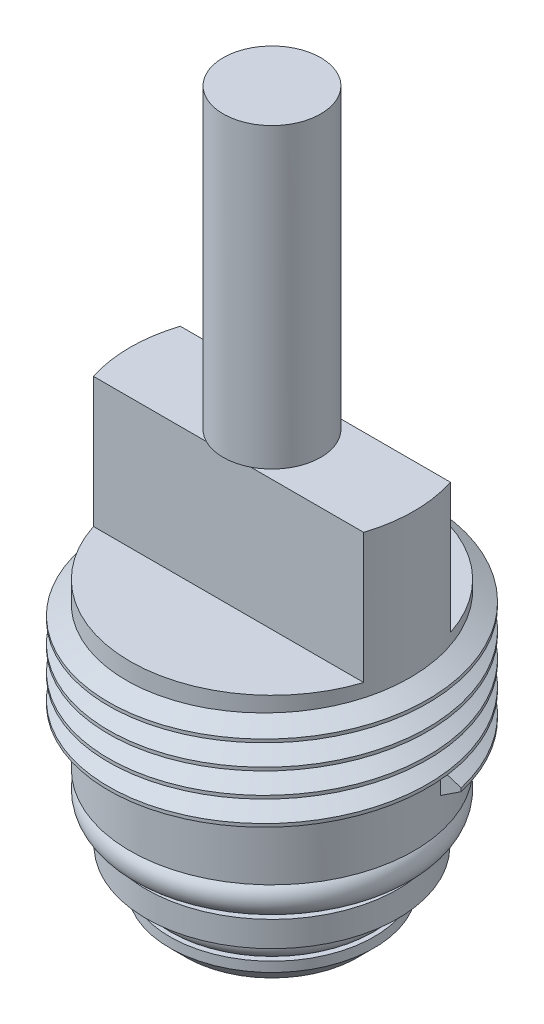
SolidWorks part; units mm, degrees
material "Brass"
ref_plane "Front Plane" through (0, 0, 0) normal (0, 0, 1) x (1, 0, 0)
ref_plane "Top Plane" through (0, 0, 0) normal (0, 1, 0) x (1, 0, 0)
ref_plane "Right Plane" through (0, 0, 0) normal (1, 0, 0) x (0, 0, -1)
sketch "Sketch1" plane through (0, 0, 0) normal (0, 0, 1) x (1, 0, 0)
  line L0 (0, -6751.5455) -> (0, 330825.7272) construction
  line L1 (2.825, -7) -> (-2.825, -7) construction
  line L2 (1.5, 13.675) -> (-1.5, 13.675)
  line L3 (1.5, 13.675) -> (1.5, 4.525)
  line L4 (1.5, 4.525) -> (-1.5, 4.525)
  line L5 (-1.5, 13.675) -> (-1.5, 4.525)
  line L6 (1.5, 13.675) -> (-1.5, 4.525) construction
  line L7 (1.5, 4.525) -> (-1.5, 13.675) construction
  line L8 (3.14, -7.425) -> (-3.14, -7.425)
  line L9 (3.14, -7.425) -> (3.14, -8.225)
  line L10 (3.14, -8.225) -> (-3.14, -8.225)
  line L11 (-3.14, -7.425) -> (-3.14, -8.225)
  line L12 (3.14, -7.425) -> (-3.14, -8.225) construction
  line L13 (3.14, -8.225) -> (-3.14, -7.425) construction
  line L14 (3.87, -5.795) -> (-3.87, -5.795)
  line L15 (3.87, -5.795) -> (3.87, -6.575)
  line L16 (3.87, -6.575) -> (-3.87, -6.575)
  line L17 (-3.87, -5.795) -> (-3.87, -6.575)
  line L18 (3.87, -5.795) -> (-3.87, -6.575) construction
  line L19 (3.87, -6.575) -> (-3.87, -5.795) construction
  line L20 (3.32, -4.525) -> (-3.32, -4.525)
  line L21 (3.32, -4.525) -> (3.32, -5.795)
  line L22 (3.32, -5.795) -> (-3.32, -5.795)
  line L23 (-3.32, -4.525) -> (-3.32, -5.795)
  line L24 (3.32, -4.525) -> (-3.32, -5.795) construction
  line L25 (3.32, -5.795) -> (-3.32, -4.525) construction
  line L26 (4.365, 4.525) -> (-4.365, 4.525)
  line L27 (4.365, 4.525) -> (4.365, -4.525)
  line L28 (4.365, -4.525) -> (-4.365, -4.525)
  line L29 (-4.365, 4.525) -> (-4.365, -4.525)
  line L30 (4.365, 4.525) -> (-4.365, -4.525) construction
  line L31 (4.365, -4.525) -> (-4.365, 4.525) construction
  line L32 (0, 13.675) -> (0, -8.225)
  circle A0 centre (-2.825, -7) radius 0.425
  circle A1 centre (2.825, -7) radius 0.425
  circle A2 centre (-3.8425, -5.0475) radius 0.5225
  circle A3 centre (3.8425, -5.0475) radius 0.5225
  point P1 (0, 9.1)
  point P8 (0, -6.185)
  point P9 (0, -7.825)
  point P18 (0, -5.16)
  point P23 (0, 0)
  point P35 (0, -7)
  dimension "D12" = 6.5
  dimension "D1" = 12.75
  dimension "D2" = 8.73
  dimension "D3" = 6.28
  dimension "D4" = 0.8
  dimension "D5" = 0.85
  dimension "D6" = 7.74
  dimension "D7" = 0.78
  dimension "D8" = 6.64
  dimension "D9" = 1.27
  dimension "D10" = 3
  dimension "D11" = 9.15
revolve "Revolve2" add sketch "Sketch1" angle 360 about L32 region at (-0.75, 9.1, 0) region at (-2.1825, 0, 0) region at (-1.66, -5.16, 0) region at (-1.935, -6.185, 0) region at (-1.57, -7.825, 0)
revolve "Revolve3" add sketch "Sketch1<5>" angle 360 about L32 region at (-3.8425, -5.0475, 0) region at (-2.825, -7, 0)
sketch "Sketch1<5>" plane through (0, 0, 0) normal (0, 0, 1) x (1, 0, 0) same geometry as "Sketch1"
sketch "Sketch2" plane through (0, 4.525, 0) normal (0, 1, 0) x (1, 0, 0)
  line L0 (0, 4.365) -> (0, -4.365) construction
  line L1 (0, 1.335) -> (0, -1.335) construction
  line L2 (4.365, 4.365) -> (-4.365, 4.365)
  line L3 (4.365, 4.365) -> (4.365, 1.335)
  line L4 (4.365, 1.335) -> (-4.365, 1.335)
  line L5 (-4.365, 4.365) -> (-4.365, 1.335)
  line L6 (4.365, 4.365) -> (-4.365, 1.335) construction
  line L7 (4.365, 1.335) -> (-4.365, 4.365) construction
  line L8 (4.365, -1.335) -> (-4.365, -1.335)
  line L9 (4.365, -1.335) -> (4.365, -4.365)
  line L10 (4.365, -4.365) -> (-4.365, -4.365)
  line L11 (-4.365, -1.335) -> (-4.365, -4.365)
  line L12 (4.365, -1.335) -> (-4.365, -4.365) construction
  line L13 (4.365, -4.365) -> (-4.365, -1.335) construction
  circle A0 centre (0, 0) radius 4.365 construction
  point P5 (0, 2.85)
  point P10 (0, -2.85)
  point P18 (0, 0)
  dimension "D1" = 2.67
extrude "Cut-Extrude1" cut sketch "Sketch2" against normal blind 4
thread "Thread1" pitch 1 method extrude profile "Thread Profile1" start angle 0, offset 0, length 3.35, pitch 0.75, diameter 8.73
ref_plane "Plane1" through (-4.365, 0.525, 0) normal (0, 0, 1) x (-1, 0, 0)
sketch "Thread Profile1" plane through (-4.365, 0.525, 0) normal (0, 0, 1) x (-1, 0, 0)
  line L0 (0, 0) -> (0, 1) construction
  line L1 (0, 0) -> (0.5413, 0.3125)
  line L2 (0.5413, 0.3125) -> (0.5413, 0.4125)
  line L3 (0.5413, 0.4125) -> (0, 0.725)
  line L4 (0.5413, 0.3625) -> (0, 0.3625) construction
  line L11 (0, 0) -> (0, 0.725)
  point P2 (0, 0)
  dimension "Pitch" = 1
  dimension "Profile_Angle" = 60
  dimension "Profile_Land" = 0.1
  dimension "Profile_Height" = 0.5413
chamfer "Chamfer1" distance 0.5 1 edges at (-3.14, -8.225, 0)
ref_plane "max_compression" through (0, 10.655, 0) normal (0, 1, 0) x (1, 0, 0)
